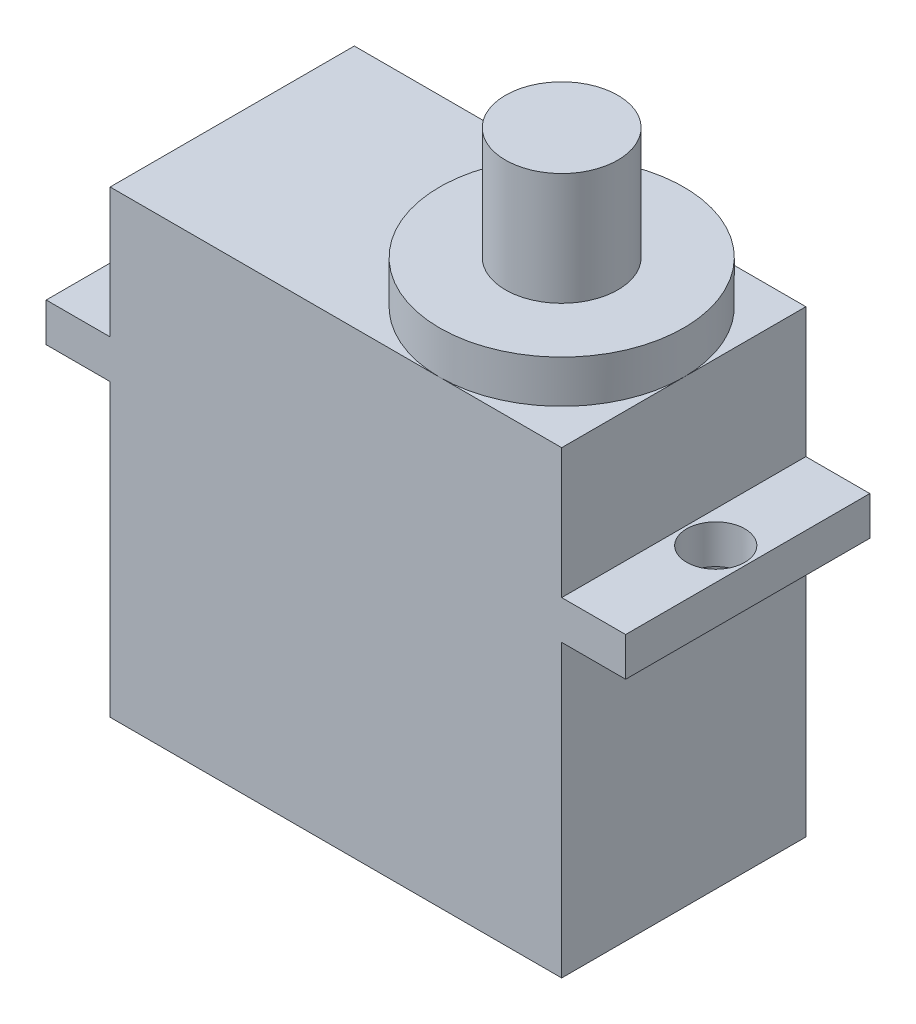
SolidWorks part; units mm, degrees
ref_plane "Front Plane" through (0, 0, 0) normal (0, 0, 1) x (1, 0, 0)
ref_plane "Top Plane" through (0, 0, 0) normal (0, 1, 0) x (1, 0, 0)
ref_plane "Right Plane" through (0, 0, 0) normal (1, 0, 0) x (0, 0, -1)
sketch "Эскиз1" plane through (0, 0, 0) normal (0, 0, 1) x (1, 0, 0)
  line L0 (0, 16.0638) -> (0, -17.3752) construction
  line L1 (-11.65, -11.85) -> (11.65, -11.85)
  line L2 (-11.65, -11.85) -> (-11.65, 3.15)
  line L3 (-11.65, 11.85) -> (11.65, 11.85)
  line L4 (11.65, -11.85) -> (11.65, 3.15)
  line L5 (-11.65, -11.85) -> (11.65, 11.85) construction
  line L6 (-11.65, 11.85) -> (11.65, -11.85) construction
  line L7 (-16.4458, 5.15) -> (16.8589, 5.15) construction
  line L8 (11.65, 5.15) -> (14.95, 5.15)
  line L9 (14.95, 5.15) -> (14.95, 3.15)
  line L10 (14.95, 3.15) -> (11.65, 3.15)
  line L11 (11.65, 5.15) -> (11.65, 11.85)
  line L12 (-11.65, 5.15) -> (-14.95, 5.15)
  line L13 (-14.95, 5.15) -> (-14.95, 3.15)
  line L14 (-14.95, 3.15) -> (-11.65, 3.15)
  line L15 (-11.65, 5.15) -> (-11.65, 11.85)
  point P0 (0, 0)
  point P10 (11.65, 5.15)
  dimension "D1" = 23.7
  dimension "D2" = 23.3
  dimension "D3" = 17
  dimension "D4" = 2
  dimension "D5" = 3.3
extrude "Бобышка-Вытянуть1" add sketch "Эскиз1" along normal mid plane 12.6
sketch "Эскиз2" plane through (0, 11.85, 0) normal (0, 1, 0) x (1, 0, 0)
  line L0 (11.65, -6.3) -> (-11.65, -6.3) construction
  line L1 (11.65, -6.3) -> (11.65, 6.3) construction
  circle A0 centre (5.35, 0) radius 6.3
  circle A1 centre (5.35, 0) radius 2.9
  dimension "D1" = 12.6
  dimension "D2" = 5.8
extrude "Бобышка-Вытянуть2" add sketch "Эскиз2" along normal blind 2.2 contours A1 | A0 A1 region at (-0.7718, 11.85, 0) region at (5.35, 11.85, 0)
extrude "Бобышка-Вытянуть3" add sketch "Эскиз2<3>" along normal blind 5.8 from surface contours A1 region at (5.35, 11.85, 0) starting at face at (5.35, 14.05, 6.3)
sketch "Эскиз2<3>" plane through (0, 11.85, 0) normal (0, 1, 0) x (1, 0, 0) same geometry as "Эскиз2"
sketch "Эскиз3" plane through (0, 5.15, 0) normal (0, 1, 0) x (1, 0, 0)
  line L0 (-11.65, 6.3) -> (-14.95, 6.3) construction
  line L1 (0, 7.9687) -> (0, -12.7883) construction
  line L2 (-14.95, -6.3) -> (-14.95, 6.3) construction
  circle A0 centre (-13.3, 0) radius 1.5
  circle A1 centre (13.3, 0) radius 1.5
  point P4 (-13.3, 6.3)
  point P11 (-14.95, 0)
  dimension "D1" = 3
extrude "Вырез-Вытянуть1" cut sketch "Эскиз3" against normal blind 5.8
